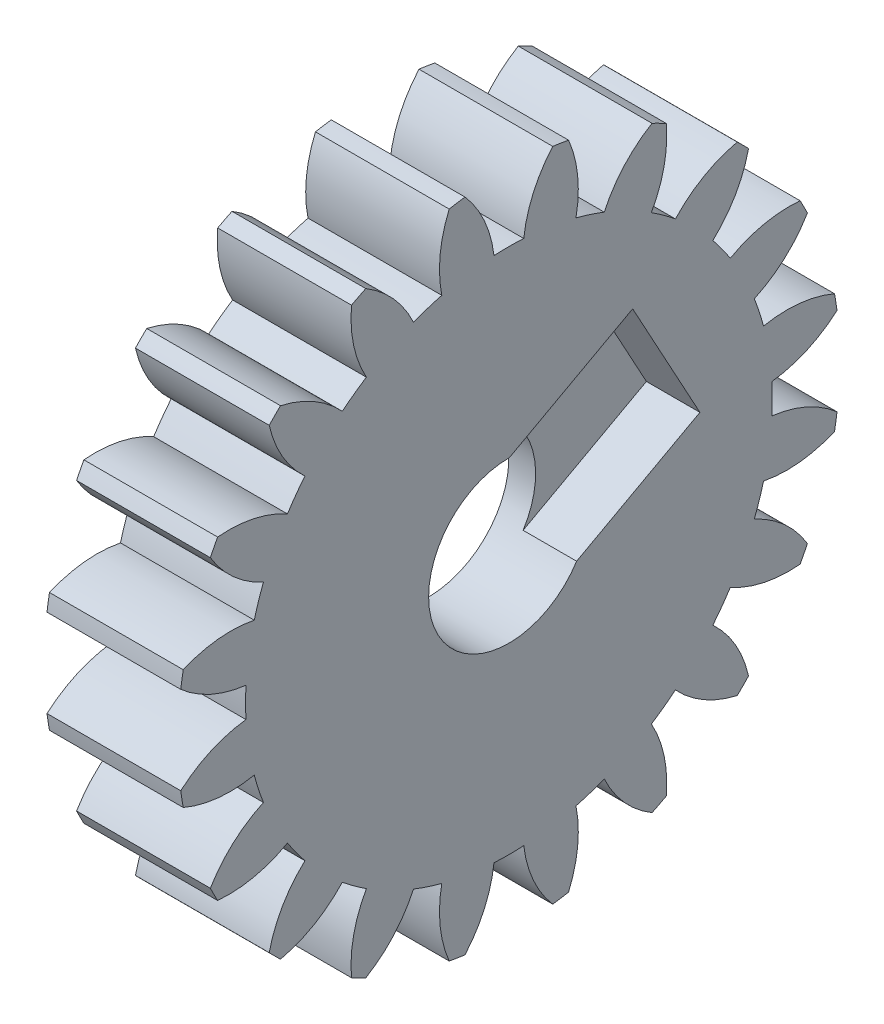
SolidWorks part; units mm, degrees
ref_plane "Plane1" through (0, 0, 0) normal (0, 0, 1) x (1, 0, 0)
ref_plane "Plane2" through (0, 0, 0) normal (0, 1, 0) x (1, 0, 0)
ref_plane "Plane3" through (0, 0, 0) normal (1, 0, 0) x (0, 0, -1)
sketch "HoldingSke" plane through (0, 0, 0) normal (0, 1, 0) x (1, 0, 0)
  line L0 (0, 0) -> (0.4176, -0.152)
  line L1 (-15, 0) -> (100, 0) construction
  line L2 (0, 0) -> (-2.1039, 2.3779)
  line L3 (0, 0) -> (-11.863, 4.5341)
  line L4 (0, 0) -> (8.1152, 2.9537)
  line L5 (0, 0) -> (-46.8476, -17.4728)
  line L6 (0, 0) -> (-8.2896, -5.593)
  line L7 (-2.1039, 2.3779) -> (8.6586, 51.2059)
  line L8 (-76.2, 54.61) -> (-76.1, 54.61)
  line L9 (-71.009, 38.7566) -> (-53.1078, 45.2721)
  line L10 (-76.2, 71.12) -> (104.1128, 71.12)
  line L11 (0, 0) -> (-10, 0)
  line L12 (-76.2, 101.6) -> (-76.123, 101.6)
  line L13 (24.9733, 27.94) -> (52.9518, 28.4284)
  line L14 (24.9733, 27.94) -> (24.9743, 27.94)
  line L15 (24.9733, 27.94) -> (100.4006, 29.5858)
  line L16 (-63.627, -2.25) -> (-12.827, -2.25)
  circle A0 centre (0, 0) radius 0.4
  circle A1 centre (0, 0) radius 19.6865
  circle A2 centre (0, 0) radius 37.5
  circle A3 centre (0, 0) radius 0.4
  dimension "MHD" = 39.373
  dimension "Hub_dia" = 75
  dimension "Bore" = 0.8
  dimension "MBD" = 0.8
  dimension "Num_teeth" = 20
  dimension "Pitch_radius" = 180.3128
  dimension "Pitch" = 0.4444
  dimension "Width" = 10
  dimension "Overall_len" = 50
  dimension "Show_teeth" = 20
  dimension "Thickness" = 10
  dimension "OAL" = 50.0001
  dimension "T_dim" = 0.1
  dimension "Ap" = 20
  dimension "H" = 19.05
  dimension "Backlash" = 0.077
  dimension "Addendum_fac" = 1
  dimension "Dedendum_fac" = 1.25
  dimension "Clearance_fac" = 0.25
  dimension "Dedendum_add" = 0.001
  dimension "Module" = 2.25
sketch "BasProSke" plane through (0, 0, 0) normal (0, 1, 0) x (1, 0, 0)
  line L0 (-10, 0) -> (60, 0) construction
  line L1 (0, 0) -> (0, 24.75)
  line L2 (0, 0) -> (10, 0)
  line L3 (10, 0) -> (10, 24.75)
  line L4 (10, 24.75) -> (0, 24.75)
  dimension "Diameter" = 49.5
  dimension "Thickness" = 10
revolve "Base-Revolve" add sketch "BasProSke" angle 360 about L0
sketch "TooCutSke" plane through (0, 0, 0) normal (1, 0, 0) x (0, 0, -1)
  line L1 (0, 0) -> (0, 107) construction
  line L2 (0, 0) -> (-1.9, 22.4196) construction
  line L3 (0, 0) -> (-7.021, 44.3291) construction
  line L4 (-1.9, 22.4196) -> (-3.5105, 22.1646) construction
  arc A0 (1.1119, 19.6551) -> (-1.1119, 19.6551) centre (0, 0) ccw
  arc A1 (3.3, 24.5546) -> (-3.3, 24.5546) centre (0, 0) ccw
  circle A2 centre (0, 0) radius 22.5 construction
  circle A3 centre (0, 0) radius 21.1431 construction
  arc A4 (-1.1119, 19.6551) -> (-3.3, 24.5546) centre (-10.0501, 18.6018) ccw
  arc A5 (3.3, 24.5546) -> (1.1119, 19.6551) centre (10.0501, 18.6018) ccw
  dimension "Root_dia" = 39.373
  dimension "Overcut_dia" = 49.5508
  dimension "Pitch_dia" = 45
  dimension "Base_dia" = 42.2862
  dimension "Flank_rad" = 9
  dimension "Half_ang" = 9
  dimension "Half_CT" = 1.6306
extrude "ToothCut" cut sketch "TooCutSke" along normal through all
fillet "Breaks" [suppressed] radius 0.045 tangent propagation no
fillet "RootFillets" [suppressed] radius 0.5635
pattern_circular "TeethCuts" count 20 over 360 about axis through (-10, 0, 0) along (1, 0, 0) of "ToothCut", "RootFillets", "Breaks"
sketch "HubNeaOneSke" plane through (0, 0, 0) normal (-1, 0, 0) x (0, 0, 1)
  circle A0 centre (0, 0) radius 19.6865
  dimension "Diameter" = 39.373
extrude "HubNearOne" [suppressed] add sketch "HubNeaOneSke" along normal blind 40.0001
sketch "HubNeaBotSke" plane through (0, 0, 0) normal (-1, 0, 0) x (0, 0, 1)
  circle A0 centre (0, 0) radius 19.6865
  dimension "Diameter" = 39.373
extrude "HubNearBoth" [suppressed] add sketch "HubNeaBotSke" along normal blind 20
ref_plane "FarPln" through (10, 0, 0) normal (1, 0, 0) x (0, 0, -1)
sketch "HubFarSke" plane through (10, 0, 0) normal (1, 0, 0) x (0, 0, -1)
  circle A0 centre (0, 0) radius 19.6865
  dimension "Diameter" = 39.373
extrude "HubFar" [suppressed] add sketch "HubFarSke" along normal blind 20
sketch "BorSke" plane through (0, 0, 0) normal (1, 0, 0) x (0, 0, -1)
  circle A0 centre (0, 0) radius 6
  dimension "Diameter" = 12
extrude "Bore" cut sketch "BorSke" along normal mid plane 100.0001
sketch "KeySke" plane through (0, 0, 0) normal (1, 0, 0) x (0, 0, -1)
  line L0 (-0.05, 0) -> (-0.05, 0.5)
  line L1 (-0.05, 0.5) -> (0.05, 0.5)
  line L2 (0.05, 0.5) -> (0.05, 0)
  line L3 (0, 0) -> (0, 34) construction
  line L4 (-0.05, 0) -> (0.05, 0)
  dimension "Offset" = 0.5
  dimension "Width" = 0.1
extrude "Keyway" [suppressed] cut sketch "KeySke" along normal mid plane 100.0001
pattern_circular "Keyway2" [suppressed] count 2 every 90 about axis through (-10, 0, 0) along (1, 0, 0) reverse direction yes
sketch "Sketch1" plane through (10, 0, 0) normal (1, 0, 0) x (0, 0, -1)
  line L0 (0.0359, 5.9999) -> (5.0641, -3.2178)
  line L1 (0.0359, 5.9999) -> (9.2536, 11.0282)
  line L2 (5.0641, -3.2178) -> (14.2819, 1.8104)
  line L3 (9.2536, 11.0282) -> (14.2819, 1.8104)
  circle A0 centre (0, 0) radius 6
  circle A1 centre (0, 0) radius 6 construction
  dimension "D1" = 0
  dimension "D4" = 12
  dimension "D2" = 6
  dimension "D3" = 6
  dimension "D5" = 10.5
  dimension "D6" = 10.5
extrude "Cut-Extrude1" cut sketch "Sketch1" against normal blind 4 contours L0 A0 | L0 A0 | A0 L0 L2 L3 L1 region at (10, 1.9994, -3.6652) region at (10, 4.4105, -8.0852) region at (10, -0.5134, 0.9411)
sketch "Sketch2" plane through (0, 0, 0) normal (-1, 0, 0) x (0, 0, 1)
  line L1 (12.4634, -6.055) -> (11.4755, 7.7661)
  line L2 (11.4755, 7.7661) -> (-0.9879, 13.8211)
  line L3 (-0.9879, 13.8211) -> (-12.4634, 6.055)
  line L4 (-12.4634, 6.055) -> (-11.4755, -7.7661)
  line L5 (-11.4755, -7.7661) -> (0.9879, -13.8211)
  line L6 (0.9879, -13.8211) -> (12.4634, -6.055)
  circle A0 centre (0, 0) radius 12 construction
  circle A1 centre (0, 0) radius 6 construction
  dimension "D1" = 0
  dimension "D2" = 24
extrude "Cut-Extrude2" cut sketch "Sketch2" against normal blind 4
equation "' \"Module@HoldingSke\" = 6.35"
equation "' \"Num_teeth@HoldingSke\" = 12"
equation "' \"Ap@HoldingSke\" =  20"
equation "' \"Width@HoldingSke\" = 0.5 * 25.4"
equation "' \"Hub_dia@HoldingSke\"= 1 * 25.4"
equation "' \"Overall_len@HoldingSke\" = 1.0 * 25.4"
equation "' \"Bore@HoldingSke\" = 0.75 * 25.4"
equation "' \"T_dim@HoldingSke\" = 0.1 * 25.4"
equation "' \"Width@KeySke\" = 0.25 * 25.4"
equation "' \"Show_teeth@HoldingSke\" = 13"
equation "' \"Backlash@HoldingSke\" = 0.009 * 25.4"
equation "' \"Addendum_fac@HoldingSke\" = 1.0"
equation "' \"Dedendum_fac@HoldingSke\" = 1.25"
equation "' \"Dedendum_add@HoldingSke\" = 0.00005 * 25.4"
equation "' \"Clearance_fac@HoldingSke\" = 0.25"
equation "\"Pitch@HoldingSke\" = 1 / \"Module@HoldingSke\""
equation "\"Overcut_dia@TooCutSke\" = (\"Num_teeth@HoldingSke\" + 2 * \"Addendum_fac@HoldingSke\") / \"Pitch@HoldingSke\" + 0.002 * 25.4"
equation "\"Pitch_dia@TooCutSke\" = \"Num_teeth@HoldingSke\" / \"Pitch@HoldingSke\""
equation "\"Base_dia@TooCutSke\" = \"Num_teeth@HoldingSke\" / \"Pitch@HoldingSke\" * cos((\"Ap@HoldingSke\"  * 3.14159265 / 180))"
equation "\"Root_dia@TooCutSke\" = (\"Num_teeth@HoldingSke\" + 2) / \"Pitch@HoldingSke\" - 2 * (\"Addendum_fac@HoldingSke\" + \"Dedendum_fac@HoldingSke\") / \"Pitch@HoldingSke\" - \"Dedendum_add@HoldingSke\" * 2"
equation "\"Half_ang@TooCutSke\" = 180 / \"Num_teeth@HoldingSke\""
equation "\"Half_CT@TooCutSke\" = \"Num_teeth@HoldingSke\" / \"Pitch@HoldingSke\" * sin((3.14159265 / 2 / \"Num_teeth@HoldingSke\")) / 2 - 7 * \"Backlash@HoldingSke\" / 4"
equation "\"Flank_rad@TooCutSke\" = \"Num_teeth@HoldingSke\" / \"Pitch@HoldingSke\" / 5"
equation "\"Radius@RootFillets\" = \"Clearance_fac@HoldingSke\" / \"Pitch@HoldingSke\" + \"Dedendum_add@HoldingSke\""
equation "\"Break_rad@Breaks\" = 0.02 / \"Pitch@HoldingSke\""
equation "\"Thickness@HoldingSke\" = \"Width@HoldingSke\""
equation "\"OAL@HoldingSke\" = \"Thickness@HoldingSke\""
equation "\"MHD@HoldingSke\" = (\"Num_teeth@HoldingSke\" + 2) / \"Pitch@HoldingSke\" - 2 * (\"Addendum_fac@HoldingSke\" + \"Dedendum_fac@HoldingSke\")  / \"Pitch@HoldingSke\" - \"Dedendum_add@HoldingSke\" * 2"
equation "\"MBD@HoldingSke\" = (\"Num_teeth@HoldingSke\" + 2) / \"Pitch@HoldingSke\" - 2 * (\"Addendum_fac@HoldingSke\" + \"Dedendum_fac@HoldingSke\")  / \"Pitch@HoldingSke\" - \"Dedendum_add@HoldingSke\" * 2 - 0.002 * 25.4"
equation "\"MHD@HoldingSke\" = ((sgn( \"MHD@HoldingSke\" - \"Hub_dia@HoldingSke\" )-1)*( \"MHD@HoldingSke\" - \"Hub_dia@HoldingSke\" ))/-2+ \"Hub_dia@HoldingSke\""
equation "\"MBD@HoldingSke\" = ((sgn( \"MBD@HoldingSke\" - \"Bore@HoldingSke\" )-1)*( \"MBD@HoldingSke\" - \"Bore@HoldingSke\" ))/-2+ \"Bore@HoldingSke\""
equation "\"OAL@HoldingSke\" = ((sgn( \"OAL@HoldingSke\" - \"Overall_len@HoldingSke\" )+1)*( \"OAL@HoldingSke\" - \"Overall_len@HoldingSke\" ))/2 + \"Overall_len@HoldingSke\" + 0.000002 * 25.4"
equation "\"Num_teeth@TeethCuts\" = int( \"Show_teeth@HoldingSke\" ) + 1"
equation "\"Num_teeth@TeethCuts\" = ((sgn( \"Num_teeth@TeethCuts\" - \"Num_teeth@HoldingSke\" )-1)*( \"Num_teeth@TeethCuts\" - \"Num_teeth@HoldingSke\" ))/-2+ \"Num_teeth@HoldingSke\""
equation "\"Num_teeth@TeethCuts\" = ((sgn( \"Num_teeth@TeethCuts\" - 2.0)+1)*( \"Num_teeth@TeethCuts\" - 2.0))/2 +2.0"
equation "\"Angle@TeethCuts\" = 360.0 / \"Num_teeth@HoldingSke\""
equation "\"Diameter@BasProSke\" = (\"Num_teeth@HoldingSke\" + 2 * \"Addendum_fac@HoldingSke\") / \"Pitch@HoldingSke\""
equation "\"Thickness@BasProSke\"  = \"Thickness@HoldingSke\""
equation "' \"Fillet_rad@BasProSke\" =  \"Thickness@HoldingSke\" * 0.05"
equation "\"MHD@HoldingSke\" = ((sgn( \"MHD@HoldingSke\" - \"Root_dia@TooCutSke\" )-1)*( \"MHD@HoldingSke\" - \"Root_dia@TooCutSke\" ))/-2+ \"Root_dia@TooCutSke\""
equation "\"Diameter@HubNeaOneSke\" = \"MHD@HoldingSke\""
equation "\"Length@HubNearOne\" = \"OAL@HoldingSke\" - \"Thickness@BasProSke\""
equation "\"Diameter@HubNeaBotSke\" = \"MHD@HoldingSke\""
equation "\"Length@HubNearBoth\" = ( \"OAL@HoldingSke\" - \"Thickness@BasProSke\" ) / 2.0"
equation "\"Thickness@FarPln\" = \"Thickness@BasProSke\""
equation "\"Diameter@HubFarSke\" = \"MHD@HoldingSke\""
equation "\"Length@HubFar\" = ( \"OAL@HoldingSke\" - \"Thickness@BasProSke\" ) / 2.0"
equation "\"Diameter@BorSke\"=12mm"
equation "\"D1@Bore\" = \"OAL@HoldingSke\" * 2.0"
equation "\"D1@Keyway\" = \"OAL@HoldingSke\" * 2.0"
equation "\"Offset@KeySke\" = \"T_dim@HoldingSke\" + \"MBD@HoldingSke\" / 2.0"
